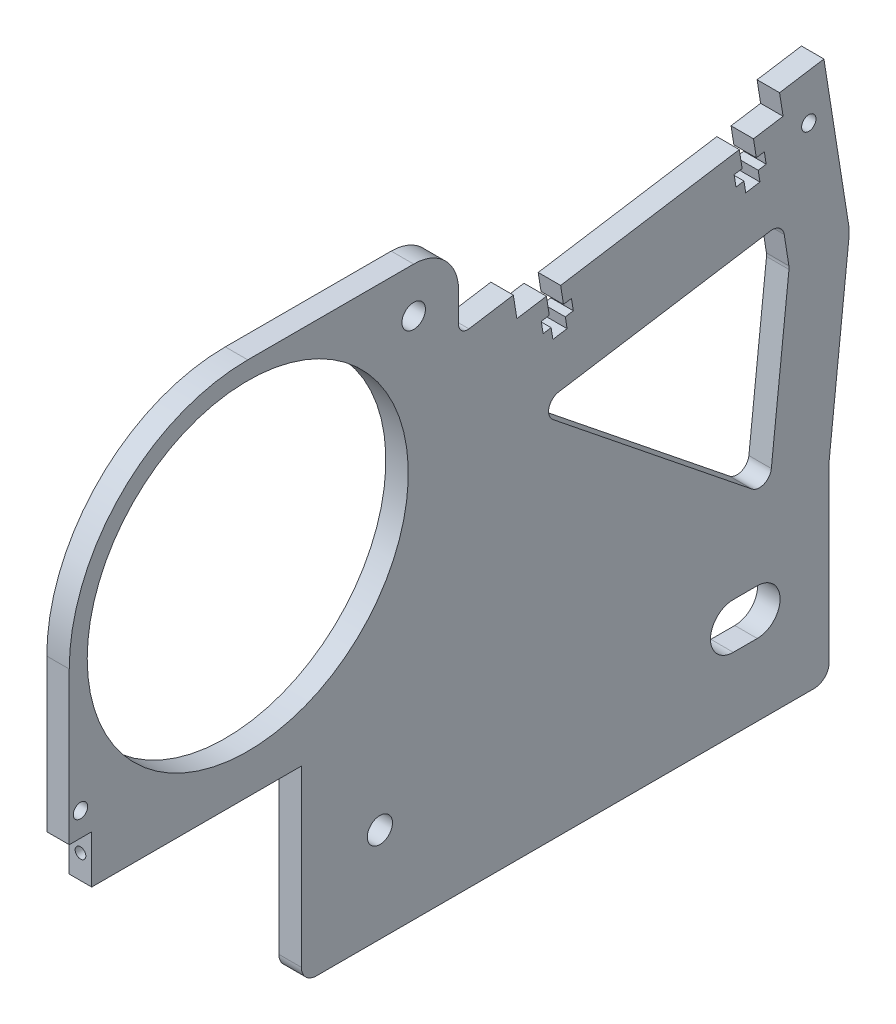
SolidWorks part; units mm, degrees
ref_plane "Front Plane" through (0, 0, 0) normal (0, 0, 1) x (1, 0, 0)
ref_plane "Top Plane" through (0, 0, 0) normal (0, 1, 0) x (1, 0, 0)
ref_plane "Right Plane" through (0, 0, 0) normal (1, 0, 0) x (0, 0, -1)
sketch "Sketch1" plane through (0, 0, 0) normal (1, 0, 0) x (0, 0, -1)
  line L0 (-28.1703, 0) -> (77.3828, 0)
  line L1 (80.5578, 3.175) -> (80.5578, 40.132)
  line L2 (-80.5578, 82.55) -> (-80.5578, 50.292)
  line L3 (24.9961, 92.2761) -> (21.9857, 91.7993) construction
  line L4 (-75.7953, 50.292) -> (-75.7953, 40.132)
  line L5 (65.3178, 20.066) -> (60.2378, 20.066) construction
  line L6 (65.3178, 15.2273) -> (60.2378, 15.2273)
  line L7 (-75.7953, 40.132) -> (-31.3453, 40.132)
  line L8 (24.6236, 94.628) -> (24.9961, 92.2761) construction
  line L9 (21.9857, 91.7993) -> (21.6131, 94.1512) construction
  line L10 (-31.3453, 40.132) -> (-31.3453, 3.175)
  line L11 (-80.5578, 50.292) -> (-75.7953, 50.292)
  line L12 (65.3178, 24.9047) -> (60.2378, 24.9047)
  line L13 (21.6131, 94.1512) -> (19.9198, 93.883) construction
  line L14 (19.9198, 93.883) -> (19.5274, 96.3604) construction
  line L15 (19.5274, 96.3604) -> (21.2208, 96.6286) construction
  line L16 (21.2208, 96.6286) -> (20.6198, 100.423) construction
  line L17 (20.6198, 100.423) -> (14.348, 99.4297) construction
  line L18 (14.348, 99.4297) -> (13.6029, 104.1335) construction
  line L19 (13.6029, 104.1335) -> (4.1952, 102.6435) construction
  line L20 (1.9922, 104.525) -> (1.9922, 110.875) construction
  line L21 (-7.5328, 120.4) -> (-42.7078, 120.4) construction
  line L22 (24.9961, 92.2761) -> (21.9857, 91.7993)
  line L23 (24.6236, 94.628) -> (24.9961, 92.2761)
  line L24 (21.9857, 91.7993) -> (21.6131, 94.1512)
  line L25 (21.6131, 94.1512) -> (19.9198, 93.883)
  line L26 (19.9198, 93.883) -> (19.5274, 96.3604)
  line L27 (19.5274, 96.3604) -> (21.2208, 96.6286)
  line L28 (21.2208, 96.6286) -> (20.6198, 100.423)
  line L29 (20.6198, 100.423) -> (14.348, 99.4297)
  line L30 (14.348, 99.4297) -> (13.6029, 104.1335)
  line L31 (13.6029, 104.1335) -> (4.1952, 102.6435)
  line L32 (1.9922, 104.525) -> (1.9922, 110.875)
  line L33 (-7.5328, 120.4) -> (-42.7078, 120.4)
  line L35 (80.5578, 40.132) -> (84.7717, 79.1961)
  line L36 (25.9246, 97.3736) -> (26.317, 94.8962) construction
  line L37 (26.317, 94.8962) -> (24.6236, 94.628) construction
  line L38 (24.2312, 97.1054) -> (25.9246, 97.3736) construction
  line L39 (23.6303, 100.8998) -> (24.2312, 97.1054) construction
  line L51 (70.0493, 113.0738) -> (70.7944, 108.3699) construction
  line L52 (79.4571, 114.5638) -> (70.0493, 113.0738) construction
  line L55 (68.3027, 44.9396) -> (72.0438, 79.6202) construction
  line L56 (68.1298, 88.6604) -> (23.2189, 81.5472) construction
  line L57 (22.0267, 77.0573) -> (64.1879, 43.2308) construction
  line L58 (84.7184, 81.3449) -> (79.4571, 114.5638) construction
  line L59 (64.5225, 107.3765) -> (65.1235, 103.5821) construction
  line L60 (25.9246, 97.3736) -> (26.317, 94.8962)
  line L61 (26.317, 94.8962) -> (24.6236, 94.628)
  line L62 (24.2312, 97.1054) -> (25.9246, 97.3736)
  line L63 (23.6303, 100.8998) -> (24.2312, 97.1054)
  line L64 (62.113, 103.1053) -> (61.5121, 106.8997) construction
  line L65 (60.4196, 102.8371) -> (62.113, 103.1053) construction
  line L66 (60.812, 100.3597) -> (60.4196, 102.8371) construction
  line L67 (62.5054, 100.6279) -> (60.812, 100.3597) construction
  line L68 (62.8779, 98.276) -> (62.5054, 100.6279) construction
  line L69 (65.8884, 98.7528) -> (62.8779, 98.276) construction
  line L70 (65.5159, 101.1047) -> (65.8884, 98.7528) construction
  line L71 (67.2093, 101.3729) -> (65.5159, 101.1047) construction
  line L72 (66.8169, 103.8503) -> (67.2093, 101.3729) construction
  line L73 (65.1235, 103.5821) -> (66.8169, 103.8503) construction
  line L74 (84.7184, 81.3449) -> (79.4571, 114.5638)
  line L75 (70.0493, 113.0738) -> (70.7944, 108.3699)
  line L76 (79.4571, 114.5638) -> (70.0493, 113.0738)
  line L77 (64.5225, 107.3765) -> (65.1235, 103.5821)
  line L79 (68.3027, 44.9396) -> (72.0438, 79.6202)
  line L80 (68.1298, 88.6604) -> (23.2189, 81.5472)
  line L81 (22.0267, 77.0573) -> (64.1879, 43.2308)
  line L82 (62.113, 103.1053) -> (61.5121, 106.8997)
  line L83 (60.4196, 102.8371) -> (62.113, 103.1053)
  line L84 (60.812, 100.3597) -> (60.4196, 102.8371)
  line L85 (62.5054, 100.6279) -> (60.812, 100.3597)
  line L86 (62.8779, 98.276) -> (62.5054, 100.6279)
  line L87 (65.8884, 98.7528) -> (62.8779, 98.276)
  line L88 (65.5159, 101.1047) -> (65.8884, 98.7528)
  line L89 (67.2093, 101.3729) -> (65.5159, 101.1047)
  line L90 (66.8169, 103.8503) -> (67.2093, 101.3729)
  line L91 (65.1235, 103.5821) -> (66.8169, 103.8503)
  line L92 (70.7944, 108.3699) -> (64.5225, 107.3765) construction
  line L93 (61.5121, 106.8997) -> (23.6303, 100.8998) construction
  line L94 (72.0272, 80.29) -> (71.0359, 86.549) construction
  line L95 (70.7944, 108.3699) -> (64.5225, 107.3765)
  line L96 (61.5121, 106.8997) -> (23.6303, 100.8998)
  line L97 (72.0272, 80.29) -> (71.0359, 86.549)
  arc A0 (65.3178, 15.2273) -> (65.3178, 24.9047) centre (65.3178, 20.066) ccw
  circle A1 centre (-42.7078, 82.55) radius 31.5 construction
  circle A2 centre (65.3178, 20.066) radius 77.47 construction
  circle A3 centre (-78.1765, 55.372) radius 1.524
  arc A4 (60.2378, 24.9047) -> (60.2378, 15.2273) centre (60.2378, 20.066) ccw
  arc A5 (-42.7078, 120.4) -> (-80.5578, 82.55) centre (-42.7078, 82.55) ccw
  arc A6 (-28.1703, 0) -> (-31.3453, 3.175) centre (-28.1703, 3.175) cw
  arc A7 (77.3828, 0) -> (80.5578, 3.175) centre (77.3828, 3.175) ccw
  circle A9 centre (76.2432, 104.411) radius 1.524 construction
  circle A10 centre (76.2432, 104.411) radius 1.524
  circle A11 centre (-14.6922, 20.066) radius 2.667
  arc A12 (1.9922, 104.525) -> (4.1952, 102.6435) centre (3.8972, 104.525) ccw construction
  arc A13 (1.9922, 110.875) -> (-7.5328, 120.4) centre (-7.5328, 110.875) ccw construction
  arc A14 (1.9922, 104.525) -> (4.1952, 102.6435) centre (3.8972, 104.525) ccw
  arc A15 (1.9922, 110.875) -> (-7.5328, 120.4) centre (-7.5328, 110.875) ccw
  circle A16 centre (-42.7078, 82.55) radius 34.04
  arc A18 (84.7717, 79.1961) -> (84.7184, 81.3449) centre (76.6695, 80.0701) ccw construction
  arc A20 (23.2189, 81.5472) -> (22.0267, 77.0573) centre (23.6162, 79.0385) ccw construction
  arc A21 (64.1879, 43.2308) -> (68.3027, 44.9396) centre (65.7774, 45.212) ccw construction
  arc A22 (71.0359, 86.549) -> (68.1298, 88.6604) centre (68.5271, 86.1517) ccw construction
  arc A23 (84.7717, 79.1961) -> (84.7184, 81.3449) centre (76.6695, 80.0701) ccw
  arc A24 (72.0438, 79.6202) -> (72.0272, 80.29) centre (69.5185, 79.8927) ccw construction
  arc A25 (23.2189, 81.5472) -> (22.0267, 77.0573) centre (23.6162, 79.0385) ccw
  arc A26 (64.1879, 43.2308) -> (68.3027, 44.9396) centre (65.7774, 45.212) ccw
  circle A29 centre (-7.5328, 110.875) radius 2.4892 construction
  circle A30 centre (-7.5328, 110.875) radius 2.4892
  arc A31 (71.0359, 86.549) -> (68.1298, 88.6604) centre (68.5271, 86.1517) ccw
  arc A32 (72.0438, 79.6202) -> (72.0272, 80.29) centre (69.5185, 79.8927) ccw
  point P13 (62.7778, 20.066)
  dimension "D4" = 9.6774
  dimension "D7" = 4.7625
  dimension "D8" = 63
  dimension "D12" = 3.175
  dimension "D14" = 2.54
  dimension "D15" = 154.94
  dimension "D18" = 5.334
  dimension "D19" = 5.08
  dimension "D17" = 3.048
  dimension "D2" = 40.132
  dimension "D3" = 20.066
  dimension "D5" = 15.24
  dimension "D6" = 44.45
  dimension "D10" = 161.1156
  dimension "D11" = 95.25
  dimension "D21" = 5.08
  dimension "D22" = 10.16
  dimension "D16" = 2.3813
extrude "Boss-Extrude1" add sketch "Sketch1" along normal blind 4.7625
sketch "Sketch2" plane through (0, 0, 75.7953) normal (0, 0, 1) x (1, 0, 0)
  line L0 (0, 50.292) -> (0, 40.132) construction
  line L1 (4.7625, 40.132) -> (0, 40.132) construction
  circle A0 centre (2.3813, 45.212) radius 1.1303
  point P4 (0, 45.212)
  point P7 (2.3813, 40.132)
  dimension "D1" = 2.2606
extrude "Cut-Extrude1" cut sketch "Sketch2" against normal blind 6.35
